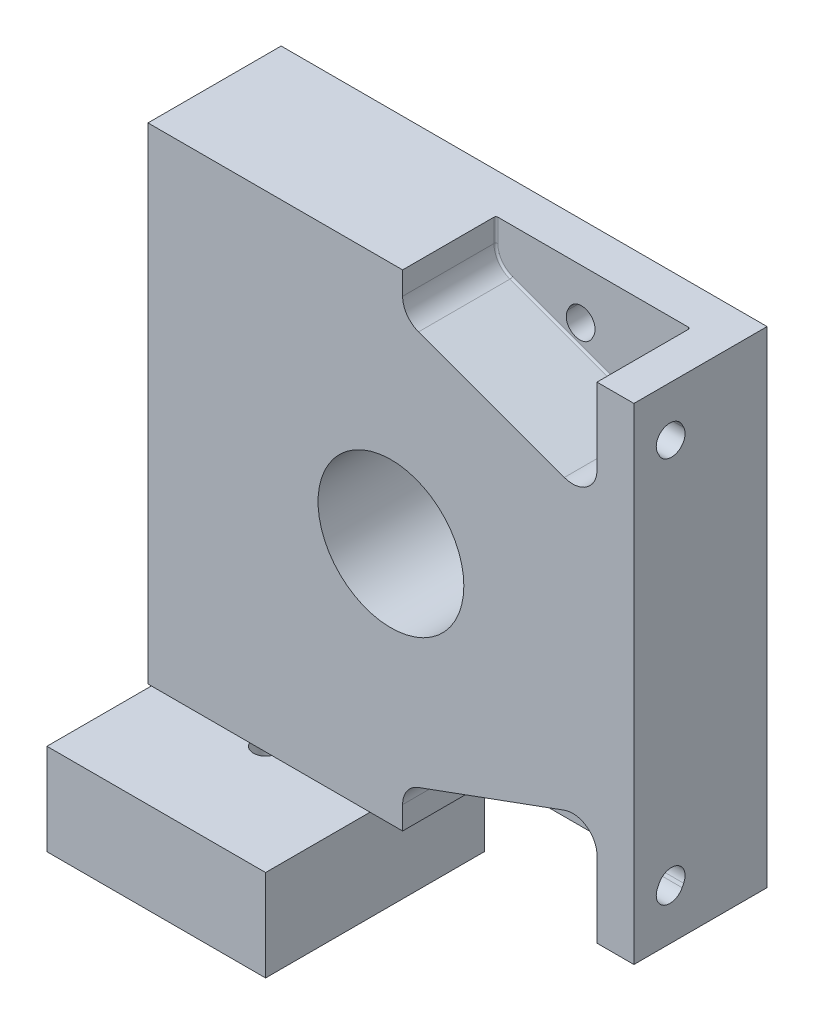
SolidWorks part; units mm, degrees
ref_plane "Front" through (0, 0, 0) normal (0, 0, 1) x (1, 0, 0)
ref_plane "Top" through (0, 0, 0) normal (0, 1, 0) x (1, 0, 0)
ref_plane "Right" through (0, 0, 0) normal (1, 0, 0) x (0, 0, -1)
sketch "Sketch2" plane through (0, 0, 0) normal (0, 0, 1) x (1, 0, 0)
  line L0 (-63.5, 63.5) -> (63.5, -63.5) construction
  line L1 (-63.5, 63.5) -> (63.5, 63.5)
  line L2 (-63.5, 63.5) -> (-63.5, -63.5)
  line L3 (-63.5, -63.5) -> (63.5, -63.5)
  line L4 (63.5, 63.5) -> (63.5, -63.5)
  dimension "D1" = 127
  dimension "D2" = 127
extrude "HOUSING" add sketch "Sketch2" along normal blind 39.5
ref_plane "Plane1" through (0, 0, 48.26) normal (0, 0, 1) x (1, 0, 0)
sketch "Sketch3" plane through (0, 0, 48.26) normal (0, 0, 1) x (1, 0, 0)
  circle A0 centre (0, 0) radius 19.05
  dimension "D1" = 38.1
sketch "Sketch4" plane through (0, 0, 39.5) normal (0, 0, 1) x (1, 0, 0)
  circle A0 centre (0, 0) radius 45.974
  dimension "D1" = 91.948
extrude "Cut-Extrude2" cut sketch "Sketch4" against normal blind 4.698 flip side to cut
sketch "Sketch8" plane through (0, 0, 34.802) normal (0, 0, 1) x (1, 0, 0)
  line L0 (3.048, -63.5) -> (3.048, -57.528)
  line L1 (-63.5, -63.5) -> (63.5, -63.5) construction
  line L2 (7.2207, -51.5629) -> (45.3207, -37.6564)
  line L3 (53.848, -43.6215) -> (53.848, -63.5)
  line L4 (-63.5, 63.5) -> (-63.5, -63.5) construction
  line L5 (3.048, -63.5) -> (53.848, -63.5)
  line L6 (0, 0) -> (83.0961, 0) construction
  line L7 (3.048, 63.5) -> (53.848, 63.5)
  line L8 (53.848, 43.6215) -> (53.848, 63.5)
  line L9 (7.2207, 51.5629) -> (45.3207, 37.6564)
  line L10 (3.048, 63.5) -> (3.048, 57.528)
  line L11 (53.848, -51.1628) -> (53.848, -17.132) construction
  line L12 (3.048, -53.086) -> (67.489, -29.5651) construction
  line L13 (3.048, -61.8074) -> (3.048, -48.2133) construction
  arc A0 (3.048, -57.528) -> (7.2207, -51.5629) centre (9.398, -57.528) cw
  arc A1 (45.3207, -37.6564) -> (53.848, -43.6215) centre (47.498, -43.6215) cw
  arc A2 (45.3207, 37.6564) -> (53.848, 43.6215) centre (47.498, 43.6215) ccw
  arc A3 (3.048, 57.528) -> (7.2207, 51.5629) centre (9.398, 57.528) ccw
  point P27 (53.848, -34.544)
  point P30 (3.048, -53.086)
  dimension "D1" = 6.35
  dimension "D2" = 50.8
  dimension "D3" = 66.548
  dimension "D4" = 28.956
  dimension "D5" = 10.414
extrude "MOUNTING POCKETS" cut sketch "Sketch8" against normal blind 24.384
sketch "Sketch21" plane through (63.5, -23.6461, 1.1666) normal (1, 0, 0) x (0, 0, -1)
  line L0 (1.1666, 111.3134) -> (1.1666, 5.23) construction
  line L1 (-54.2716, 23.6461) -> (63.3306, 23.6461) construction
  line L2 (-20.6415, 75.2421) -> (-21.0415, 76.0421)
  line L3 (-27.0254, 72.0502) -> (-27.4254, 72.8502)
  line L4 (1.1666, -39.8539) -> (1.1666, 87.1461) construction
  line L5 (-27.0254, -24.7579) -> (-27.4254, -25.5579)
  line L6 (-20.6415, -27.9498) -> (-21.0415, -28.7498)
  arc A0 (-21.0415, 76.0421) -> (-27.4254, 72.8502) centre (-24.2334, 74.4461) ccw
  arc A1 (-27.0254, 72.0502) -> (-20.6415, 75.2421) centre (-23.8334, 73.6461) ccw
  arc A2 (-27.0254, -24.7579) -> (-20.6415, -27.9498) centre (-23.8334, -26.3539) cw
  arc A3 (-21.0415, -28.7498) -> (-27.4254, -25.5579) centre (-24.2334, -27.1539) cw
  dimension "HORIZ METRIC DIST" = 25
  dimension "HORIZ ENG DIST" = 25.4
  dimension "VERTICAL METRIC DIST" = 50
  dimension "VERT ENG DIST" = 50.8
extrude "ENG_METRIC SLOT VERTICAL" cut sketch "Sketch21" against normal up to next
sketch "Sketch212" plane through (34.0621, -104.656, 0) normal (0, 0, -1) x (-1, 0, 0)
  line L0 (34.0621, 192.3232) -> (34.0621, 86.2399) construction
  line L1 (-54.2716, 104.656) -> (63.3306, 104.656) construction
  line L2 (12.254, 156.252) -> (11.854, 157.052)
  line L3 (5.8701, 153.06) -> (5.4701, 153.86)
  line L4 (5.8701, 56.252) -> (5.4701, 55.452)
  line L5 (12.254, 53.06) -> (11.854, 52.26)
  arc A0 (11.854, 157.052) -> (5.4701, 153.86) centre (8.6621, 155.456) ccw
  arc A1 (5.8701, 153.06) -> (12.254, 156.252) centre (9.0621, 154.656) ccw
  arc A2 (5.8701, 56.252) -> (12.254, 53.06) centre (9.0621, 54.656) cw
  arc A3 (11.854, 52.26) -> (5.4701, 55.452) centre (8.6621, 53.856) cw
  dimension "HORIZ METRIC DIST" = 25
  dimension "HORIZ ENG DIST" = 25.4
  dimension "VERTICAL METRIC DIST" = 50
  dimension "VERT ENG DIST" = 50.8
extrude "ENG_METRIC SLOT HORIZONTAL" cut sketch "Sketch212" against normal through all
fillet "Fillet3" radius 0.508 10 edges at (53.848, 53.5608, 10.418) (51.1378, 38.4182, 10.418) (26.2707, 44.6097, 10.418) (4.1947, 53.8882, 10.418) (3.048, 60.514, 10.418) (53.848, -53.5608, 10.418) (51.1378, -38.4182, 10.418) (26.2707, -44.6097, 10.418) (4.1947, -53.8882, 10.418) (3.048, -60.514, 10.418)
sketch "Sketch213" plane through (0, -63.5, 0) normal (0, -1, 0) x (1, 0, 0)
  line L0 (-63.5, 0) -> (63.5, 0) construction
  line L1 (-65.659, 1.905) -> (-8.509, 1.905)
  line L2 (-65.659, 1.905) -> (-65.659, 59.055)
  line L3 (-65.659, 59.055) -> (-8.509, 59.055)
  line L4 (-8.509, 1.905) -> (-8.509, 59.055)
  dimension "D1" = 57.15
  dimension "D2" = 57.15
  dimension "D3" = 1.905
  dimension "D4" = 8.509
extrude "Extrude1" add sketch "Sketch213" along normal blind 26.924
sketch "Sketch214" plane through (0, -90.424, 0) normal (0, -1, 0) x (1, 0, 0)
  line L0 (-65.659, 1.905) -> (-8.509, 1.905) construction
  line L1 (-65.659, 59.055) -> (-65.659, 1.905) construction
  circle A0 centre (-37.084, 30.48) radius 23.8125
  dimension "D3" = 47.625
  dimension "D1" = 28.575
  dimension "D2" = 28.575
extrude "Cut-Extrude3" cut sketch "Sketch214" against normal blind 5
sketch "Sketch215" plane through (0, -85.424, 0) normal (0, -1, 0) x (1, 0, 0)
  circle A0 centre (-37.084, 30.48) radius 3.175
  circle A1 centre (-37.084, 30.48) radius 23.8125 construction
  dimension "D1" = 6.35
extrude "Cut-Extrude4" cut sketch "Sketch215" against normal up to surface (21.924 mm away) up to face at (12.8058, -63.5, 15.458)
sketch "Sketch216" plane through (-65.659, 0, 0) normal (-1, 0, 0) x (0, 0, 1)
  line L1 (59.055, -63.5) -> (16.51, -63.5)
  line L2 (59.055, -63.5) -> (59.055, -66.548)
  line L3 (59.055, -66.548) -> (16.51, -66.548)
  line L4 (16.51, -63.5) -> (16.51, -66.548)
  dimension "D1" = 3.048
extrude "Cut-Extrude5" cut sketch "Sketch216" against normal up to next
hole_wizard "#8-32 Tapped Hole1" positions "Sketch218" profile "Sketch217" tap size "#8-32" standard "Ansi Inch"
sketch "Sketch218" plane through (0, -90.424, 0) normal (0, -1, 0) x (1, 0, 0)
  line L0 (-37.084, 30.48) -> (-37.084, 29.6778) construction
  line L1 (-19.7801, 30.48) -> (-37.084, 30.48) construction
  circle A0 centre (-37.084, 30.48) radius 3.175 construction
  point P0 (-60.706, 6.858)
  point P7 (-60.706, 54.102)
  point P8 (-13.462, 54.102)
  point P9 (-13.462, 6.858)
  dimension "D1" = 23.622
  dimension "D2" = 23.622
sketch "Sketch217" plane through (-60.706, -90.424, 6.858) normal (1, 0, 0) x (0, 0, -1)
  line L0 (0, 0) -> (0, 11.7464)
  line L1 (0, 11.7464) -> (1.7272, 10.7086)
  line L2 (1.7272, 10.7086) -> (1.7272, 0)
  line L5 (1.7272, 0) -> (0, 0)
  line L10 (0, 11.7464) -> (-1.7272, 10.7086) construction
  line L11 (0, -6.35) -> (0, 107.95) construction
  dimension "Tap Drill Dia." = 3.4544
  dimension "Tap Drill Depth" = 10.7086
  dimension "Drill Angle" = 118
cosmetic thread "Cosmetic Thread1" parameters "D1"=8.3312, "D2"=4.1656
sketch "Sketch239" plane through (-63.5, -121.6811, -83.5661) normal (-1, 0, 0) x (0, 0, 1)
  line L0 (102.3006, 124.3698) -> (102.3006, 122.0362)
  line L1 (101.5379, 121.2735) -> (100.4208, 121.2735)
  line L2 (99.6339, 122.0604) -> (99.6339, 124.195)
  line L3 (100.4552, 125.0162) -> (101.5379, 125.0162)
  line L4 (101.6546, 123.1805) -> (101.6546, 122.3531)
  line L5 (101.4072, 122.1057) -> (100.5491, 122.1057)
  line L6 (100.3049, 122.3499) -> (100.3049, 123.8847)
  line L7 (100.5701, 124.1499) -> (101.4117, 124.1499)
  line L8 (101.659, 123.901) -> (101.6546, 123.1805)
  line L9 (101.6214, 127.7512) -> (101.6214, 126.2045)
  line L10 (101.4803, 126.0635) -> (101.1416, 126.0635)
  line L11 (100.9953, 126.2098) -> (100.9953, 127.7512)
  line L12 (100.9953, 127.7512) -> (101.6214, 127.7512)
  line L13 (102.3006, 128.5943) -> (102.3006, 125.7347)
  line L14 (101.7926, 125.2267) -> (101.2545, 125.2267)
  line L15 (99.6339, 125.2267) -> (99.6339, 126.0693)
  line L16 (99.6339, 126.0693) -> (100.1002, 126.0693)
  line L17 (100.3288, 126.2979) -> (100.3288, 127.7582)
  line L18 (100.3288, 127.7582) -> (99.6339, 127.7582)
  line L19 (99.6339, 127.7582) -> (99.6339, 128.5943)
  line L20 (99.6339, 128.5943) -> (102.3006, 128.5943)
  line L21 (101.3052, 111.8683) -> (101.3052, 111.033)
  line L22 (101.3052, 111.033) -> (101.7294, 111.033)
  line L23 (102.3006, 111.6043) -> (102.3006, 113.7376)
  line L24 (101.5923, 114.4459) -> (100.3232, 114.4459)
  line L25 (99.6339, 113.7566) -> (99.6339, 111.4732)
  line L26 (100.1192, 110.9879) -> (100.6227, 110.9879)
  line L27 (100.6227, 110.9879) -> (100.6227, 111.8368)
  line L28 (100.6227, 111.8368) -> (100.4696, 111.8368)
  line L29 (100.2358, 112.0705) -> (100.2358, 113.3006)
  line L30 (100.5426, 113.6074) -> (101.3217, 113.6074)
  line L31 (101.6185, 113.3107) -> (101.6185, 112.0939)
  line L32 (101.3929, 111.8683) -> (101.3052, 111.8683)
  line L33 (99.6339, 136.1587) -> (102.3006, 134.699)
  line L34 (102.3006, 134.699) -> (102.3006, 133.4017)
  line L35 (102.3006, 133.4017) -> (99.6339, 131.9711)
  line L36 (99.6339, 131.9711) -> (99.6339, 132.9287)
  line L37 (99.6339, 132.9287) -> (100.0922, 133.1628)
  line L38 (100.0922, 133.1628) -> (100.0922, 134.9283)
  line L39 (100.0922, 134.9283) -> (99.6339, 135.1676)
  line L40 (99.6339, 135.1676) -> (99.6339, 136.1587)
  line L41 (100.7046, 134.6309) -> (100.7046, 133.468)
  line L42 (100.7046, 133.468) -> (101.6586, 133.9731)
  line L43 (101.6586, 133.9731) -> (101.6586, 134.1258)
  line L44 (101.6586, 134.1258) -> (100.7046, 134.6309)
  line L45 (102.3006, 131.8571) -> (102.3006, 128.8708)
  line L46 (102.3006, 128.8708) -> (101.6626, 128.8708)
  line L47 (101.6626, 128.8708) -> (101.6626, 131.0623)
  line L48 (101.6626, 131.0623) -> (101.2925, 131.0623)
  line L49 (101.2925, 131.0623) -> (101.2925, 128.9844)
  line L50 (101.2925, 128.9844) -> (100.693, 128.9844)
  line L51 (100.693, 128.9844) -> (100.693, 131.0623)
  line L52 (100.693, 131.0623) -> (100.2774, 131.0623)
  line L53 (100.2774, 131.0623) -> (100.2774, 128.8708)
  line L54 (100.2774, 128.8708) -> (99.6339, 128.8708)
  line L55 (99.6339, 128.8708) -> (99.6339, 131.8571)
  line L56 (99.6339, 131.8571) -> (102.3006, 131.8571)
  line L57 (102.3006, 121.1265) -> (102.3006, 117.8159)
  line L58 (102.3006, 117.8159) -> (101.6106, 117.8159)
  line L59 (101.6106, 117.8159) -> (101.6106, 119.0485)
  line L60 (101.6106, 119.0485) -> (99.6339, 119.0485)
  line L61 (99.6339, 119.0485) -> (99.6339, 119.9334)
  line L62 (99.6339, 119.9334) -> (101.6102, 119.9334)
  line L63 (101.6102, 119.9334) -> (101.6102, 121.1265)
  line L64 (101.6102, 121.1265) -> (102.3006, 121.1265)
  line L65 (102.3006, 117.6536) -> (102.3006, 114.6497)
  line L66 (102.3006, 114.6497) -> (101.6621, 114.6497)
  line L67 (101.6621, 114.6497) -> (101.6621, 116.8274)
  line L68 (101.6621, 116.8274) -> (101.2997, 116.8274)
  line L69 (101.2997, 116.8274) -> (101.2997, 114.7563)
  line L70 (101.2997, 114.7563) -> (100.6993, 114.7563)
  line L71 (100.6993, 114.7563) -> (100.6993, 116.8274)
  line L72 (100.6993, 116.8274) -> (100.2804, 116.8274)
  line L73 (100.2804, 116.8274) -> (100.2804, 114.6497)
  line L74 (100.2804, 114.6497) -> (99.6339, 114.6497)
  line L75 (99.6339, 114.6497) -> (99.6339, 117.6536)
  line L76 (99.6339, 117.6536) -> (102.3006, 117.6536)
  line L77 (102.3006, 110.7071) -> (102.3006, 109.8385)
  line L78 (102.3006, 109.8385) -> (101.3454, 109.8385)
  line L79 (101.3454, 109.8385) -> (101.3454, 108.0035)
  line L80 (101.3454, 108.0035) -> (102.3006, 108.0035)
  line L81 (102.3006, 108.0035) -> (102.3006, 107.1132)
  line L82 (102.3006, 107.1132) -> (99.6339, 107.1132)
  line L83 (99.6339, 107.1132) -> (99.6339, 108.0035)
  line L84 (99.6339, 108.0035) -> (100.5967, 108.0035)
  line L85 (100.5967, 108.0035) -> (100.5967, 109.8385)
  line L86 (100.5967, 109.8385) -> (99.6339, 109.8385)
  line L87 (99.6339, 109.8385) -> (99.6339, 110.7071)
  line L88 (99.6339, 110.7071) -> (102.3006, 110.7071)
  line L89 (98.9126, 131.6685) -> (98.9126, 128.6152)
  line L90 (98.9126, 128.6152) -> (91.9852, 121.7251)
  line L91 (91.9852, 121.7251) -> (96.8043, 116.8798)
  line L92 (96.8043, 116.8798) -> (96.8043, 124.7941)
  line L93 (96.8043, 124.7941) -> (98.9126, 126.8817)
  line L94 (98.9126, 126.8817) -> (98.9126, 111.5851)
  line L95 (98.9126, 111.5851) -> (88.8711, 121.6811)
  line L96 (88.8711, 121.6811) -> (98.9126, 131.6685)
  line L97 (103.0216, 131.6685) -> (113.0631, 121.6811)
  line L98 (113.0631, 121.6811) -> (103.0216, 111.5851)
  line L99 (103.0216, 131.6685) -> (103.0216, 128.6152)
  line L100 (103.0216, 128.6152) -> (109.985, 121.6893)
  line L101 (109.985, 121.6893) -> (105.1659, 116.844)
  line L102 (105.1659, 116.844) -> (105.1659, 124.7583)
  line L103 (105.1659, 124.7583) -> (103.0216, 126.8089)
  line L104 (103.0216, 126.8089) -> (103.0216, 111.5851)
  line L105 (100.3283, 125.2267) -> (99.6339, 125.2267)
  line L106 (118.3681, 121.6811) -> (83.5661, 121.6811) construction
  line L107 (118.3681, 75.7071) -> (118.3681, 167.6551) construction
  line L108 (113.0631, 121.6811) -> (88.8711, 121.6811) construction
  arc A0 (102.3006, 122.0362) -> (101.5379, 121.2735) centre (101.5379, 122.0362) cw
  arc A1 (100.4208, 121.2735) -> (99.6339, 122.0604) centre (100.4208, 122.0604) cw
  arc A2 (99.6339, 124.195) -> (100.4552, 125.0162) centre (100.4552, 124.195) cw
  arc A3 (101.5379, 125.0162) -> (102.3006, 124.3698) centre (101.5379, 124.2431) cw
  arc A4 (101.6546, 122.3531) -> (101.4072, 122.1057) centre (101.4072, 122.3531) cw
  arc A5 (100.5491, 122.1057) -> (100.3049, 122.3499) centre (100.5491, 122.3499) cw
  arc A6 (100.3049, 123.8847) -> (100.5701, 124.1499) centre (100.5701, 123.8847) cw
  arc A7 (101.4117, 124.1499) -> (101.659, 123.901) centre (101.4117, 123.9025) cw
  arc A8 (101.6214, 126.2045) -> (101.4803, 126.0635) centre (101.4803, 126.2045) cw
  arc A9 (101.1416, 126.0635) -> (100.9953, 126.2098) centre (101.1416, 126.2098) cw
  arc A10 (100.1002, 126.0693) -> (100.3288, 126.2979) centre (100.1002, 126.2979) ccw
  arc A11 (101.7926, 125.2267) -> (102.3006, 125.7347) centre (101.7926, 125.7347) ccw
  arc A12 (101.2545, 125.2267) -> (100.7973, 125.6839) centre (101.2545, 125.6839) cw
  arc A13 (100.7973, 125.6839) -> (100.3283, 125.2267) centre (100.34, 125.6839) cw
  arc A14 (101.7294, 111.033) -> (102.3006, 111.6043) centre (101.7294, 111.6043) ccw
  arc A15 (102.3006, 113.7376) -> (101.5923, 114.4459) centre (101.5923, 113.7376) ccw
  arc A16 (100.3232, 114.4459) -> (99.6339, 113.7566) centre (100.3232, 113.7566) ccw
  arc A17 (99.6339, 111.4732) -> (100.1192, 110.9879) centre (100.1192, 111.4732) ccw
  arc A18 (100.4696, 111.8368) -> (100.2358, 112.0705) centre (100.4696, 112.0705) cw
  arc A19 (100.2358, 113.3006) -> (100.5426, 113.6074) centre (100.5426, 113.3006) cw
  arc A20 (101.3217, 113.6074) -> (101.6185, 113.3107) centre (101.3217, 113.3107) cw
  arc A21 (101.6185, 112.0939) -> (101.3929, 111.8683) centre (101.3929, 112.0939) cw
extrude "AEROTECH5" [suppressed] cut sketch "Sketch239" against normal blind 0.1
sketch "Sketch240" plane through (80.6623, 63.5, -107.4581) normal (0, 1, 0) x (-1, 0, 0)
  line L0 (108.1996, 126.0312) -> (110.5333, 126.0312)
  line L1 (111.2959, 125.2686) -> (111.2959, 124.1515)
  line L2 (110.509, 123.3646) -> (108.3744, 123.3646)
  line L3 (107.5532, 124.1858) -> (107.5532, 125.2685)
  line L4 (109.3889, 125.3852) -> (110.2163, 125.3852)
  line L5 (110.4637, 125.1378) -> (110.4637, 124.2797)
  line L6 (110.2195, 124.0355) -> (108.6847, 124.0355)
  line L7 (108.4195, 124.3007) -> (108.4195, 125.1423)
  line L8 (108.6684, 125.3896) -> (109.3889, 125.3852)
  line L9 (104.8182, 125.352) -> (106.3649, 125.352)
  line L10 (106.5059, 125.211) -> (106.5059, 124.8722)
  line L11 (106.3597, 124.726) -> (104.8182, 124.726)
  line L12 (104.8182, 124.726) -> (104.8182, 125.352)
  line L13 (103.9751, 126.0312) -> (106.8348, 126.0312)
  line L14 (107.3428, 125.5232) -> (107.3428, 124.9851)
  line L15 (107.3428, 123.3646) -> (106.5001, 123.3646)
  line L16 (106.5001, 123.3646) -> (106.5001, 123.8308)
  line L17 (106.2715, 124.0594) -> (104.8112, 124.0594)
  line L18 (104.8112, 124.0594) -> (104.8112, 123.3646)
  line L19 (104.8112, 123.3646) -> (103.9751, 123.3646)
  line L20 (103.9751, 123.3646) -> (103.9751, 126.0312)
  line L21 (120.7011, 125.0358) -> (121.5364, 125.0358)
  line L22 (121.5364, 125.0358) -> (121.5364, 125.46)
  line L23 (120.9652, 126.0312) -> (118.8318, 126.0312)
  line L24 (118.1235, 125.3229) -> (118.1235, 124.0538)
  line L25 (118.8128, 123.3646) -> (121.0962, 123.3646)
  line L26 (121.5815, 123.8498) -> (121.5815, 124.3533)
  line L27 (121.5815, 124.3533) -> (120.7327, 124.3533)
  line L28 (120.7327, 124.3533) -> (120.7327, 124.2002)
  line L29 (120.4989, 123.9664) -> (119.2688, 123.9664)
  line L30 (118.962, 124.2732) -> (118.962, 125.0523)
  line L31 (119.2587, 125.3491) -> (120.4755, 125.3491)
  line L32 (120.7011, 125.1235) -> (120.7011, 125.0358)
  line L33 (96.4107, 123.3646) -> (97.8704, 126.0312)
  line L34 (97.8704, 126.0312) -> (99.1677, 126.0312)
  line L35 (99.1677, 126.0312) -> (100.5983, 123.3646)
  line L36 (100.5983, 123.3646) -> (99.6408, 123.3646)
  line L37 (99.6408, 123.3646) -> (99.4066, 123.8228)
  line L38 (99.4066, 123.8228) -> (97.6412, 123.8228)
  line L39 (97.6412, 123.8228) -> (97.4018, 123.3646)
  line L40 (97.4018, 123.3646) -> (96.4107, 123.3646)
  line L41 (97.9385, 124.4352) -> (99.1014, 124.4352)
  line L42 (99.1014, 124.4352) -> (98.5963, 125.3892)
  line L43 (98.5963, 125.3892) -> (98.4436, 125.3892)
  line L44 (98.4436, 125.3892) -> (97.9385, 124.4352)
  line L45 (100.7123, 126.0312) -> (103.6986, 126.0312)
  line L46 (103.6986, 126.0312) -> (103.6986, 125.3933)
  line L47 (103.6986, 125.3933) -> (101.5071, 125.3933)
  line L48 (101.5071, 125.3933) -> (101.5071, 125.0231)
  line L49 (101.5071, 125.0231) -> (103.585, 125.0231)
  line L50 (103.585, 125.0231) -> (103.585, 124.4236)
  line L51 (103.585, 124.4236) -> (101.5071, 124.4236)
  line L52 (101.5071, 124.4236) -> (101.5071, 124.008)
  line L53 (101.5071, 124.008) -> (103.6986, 124.008)
  line L54 (103.6986, 124.008) -> (103.6986, 123.3646)
  line L55 (103.6986, 123.3646) -> (100.7123, 123.3646)
  line L56 (100.7123, 123.3646) -> (100.7123, 126.0312)
  line L57 (111.4429, 126.0312) -> (114.7535, 126.0312)
  line L58 (114.7535, 126.0312) -> (114.7535, 125.3412)
  line L59 (114.7535, 125.3412) -> (113.5209, 125.3412)
  line L60 (113.5209, 125.3412) -> (113.5209, 123.3646)
  line L61 (113.5209, 123.3646) -> (112.636, 123.3646)
  line L62 (112.636, 123.3646) -> (112.636, 125.3408)
  line L63 (112.636, 125.3408) -> (111.4429, 125.3408)
  line L64 (111.4429, 125.3408) -> (111.4429, 126.0312)
  line L65 (114.9158, 126.0312) -> (117.9197, 126.0312)
  line L66 (117.9197, 126.0312) -> (117.9197, 125.3927)
  line L67 (117.9197, 125.3927) -> (115.742, 125.3927)
  line L68 (115.742, 125.3927) -> (115.742, 125.0303)
  line L69 (115.742, 125.0303) -> (117.8131, 125.0303)
  line L70 (117.8131, 125.0303) -> (117.8131, 124.43)
  line L71 (117.8131, 124.43) -> (115.742, 124.43)
  line L72 (115.742, 124.43) -> (115.742, 124.0111)
  line L73 (115.742, 124.0111) -> (117.9197, 124.0111)
  line L74 (117.9197, 124.0111) -> (117.9197, 123.3646)
  line L75 (117.9197, 123.3646) -> (114.9158, 123.3646)
  line L76 (114.9158, 123.3646) -> (114.9158, 126.0312)
  line L77 (121.8623, 126.0312) -> (122.7309, 126.0312)
  line L78 (122.7309, 126.0312) -> (122.7309, 125.076)
  line L79 (122.7309, 125.076) -> (124.5659, 125.076)
  line L80 (124.5659, 125.076) -> (124.5659, 126.0312)
  line L81 (124.5659, 126.0312) -> (125.4563, 126.0312)
  line L82 (125.4563, 126.0312) -> (125.4563, 123.3646)
  line L83 (125.4563, 123.3646) -> (124.5659, 123.3646)
  line L84 (124.5659, 123.3646) -> (124.5659, 124.3273)
  line L85 (124.5659, 124.3273) -> (122.7309, 124.3273)
  line L86 (122.7309, 124.3273) -> (122.7309, 123.3646)
  line L87 (122.7309, 123.3646) -> (121.8623, 123.3646)
  line L88 (121.8623, 123.3646) -> (121.8623, 126.0312)
  line L89 (100.9009, 122.6432) -> (103.9543, 122.6432)
  line L90 (103.9543, 122.6432) -> (110.8443, 115.7158)
  line L91 (110.8443, 115.7158) -> (115.6896, 120.535)
  line L92 (115.6896, 120.535) -> (107.7753, 120.535)
  line L93 (107.7753, 120.535) -> (105.6877, 122.6432)
  line L94 (105.6877, 122.6432) -> (120.9843, 122.6432)
  line L95 (120.9843, 122.6432) -> (110.8883, 112.6017)
  line L96 (110.8883, 112.6017) -> (100.9009, 122.6432)
  line L97 (100.9009, 126.7523) -> (110.8883, 136.7938)
  line L98 (110.8883, 136.7938) -> (120.9843, 126.7523)
  line L99 (100.9009, 126.7523) -> (103.9543, 126.7523)
  line L100 (103.9543, 126.7523) -> (110.8801, 133.7157)
  line L101 (110.8801, 133.7157) -> (115.7254, 128.8965)
  line L102 (115.7254, 128.8965) -> (107.8111, 128.8965)
  line L103 (107.8111, 128.8965) -> (105.7606, 126.7523)
  line L104 (105.7606, 126.7523) -> (120.9843, 126.7523)
  line L105 (107.3428, 124.059) -> (107.3428, 123.3646)
  line L106 (110.8883, 136.7938) -> (110.8883, 112.6017) construction
  line L107 (110.8883, 142.2601) -> (110.8883, 107.4581) construction
  line L108 (77.6143, 142.2601) -> (144.1623, 142.2601) construction
  line L109 (17.1623, 107.4581) -> (144.1623, 107.4581) construction
  arc A0 (110.5333, 126.0312) -> (111.2959, 125.2686) centre (110.5333, 125.2686) cw
  arc A1 (111.2959, 124.1515) -> (110.509, 123.3646) centre (110.509, 124.1515) cw
  arc A2 (108.3744, 123.3646) -> (107.5532, 124.1858) centre (108.3744, 124.1858) cw
  arc A3 (107.5532, 125.2685) -> (108.1996, 126.0312) centre (108.3264, 125.2685) cw
  arc A4 (110.2163, 125.3852) -> (110.4637, 125.1378) centre (110.2163, 125.1378) cw
  arc A5 (110.4637, 124.2797) -> (110.2195, 124.0355) centre (110.2195, 124.2797) cw
  arc A6 (108.6847, 124.0355) -> (108.4195, 124.3007) centre (108.6847, 124.3007) cw
  arc A7 (108.4195, 125.1423) -> (108.6684, 125.3896) centre (108.6669, 125.1423) cw
  arc A8 (106.3649, 125.352) -> (106.5059, 125.211) centre (106.3649, 125.211) cw
  arc A9 (106.5059, 124.8722) -> (106.3597, 124.726) centre (106.3597, 124.8722) cw
  arc A10 (106.5001, 123.8308) -> (106.2715, 124.0594) centre (106.2715, 123.8308) ccw
  arc A11 (107.3428, 125.5232) -> (106.8348, 126.0312) centre (106.8348, 125.5232) ccw
  arc A12 (107.3428, 124.9851) -> (106.8856, 124.5279) centre (106.8856, 124.9851) cw
  arc A13 (106.8856, 124.5279) -> (107.3428, 124.059) centre (106.8856, 124.0706) cw
  arc A14 (121.5364, 125.46) -> (120.9652, 126.0312) centre (120.9652, 125.46) ccw
  arc A15 (118.8318, 126.0312) -> (118.1235, 125.3229) centre (118.8318, 125.3229) ccw
  arc A16 (118.1235, 124.0538) -> (118.8128, 123.3646) centre (118.8128, 124.0538) ccw
  arc A17 (121.0962, 123.3646) -> (121.5815, 123.8498) centre (121.0962, 123.8498) ccw
  arc A18 (120.7327, 124.2002) -> (120.4989, 123.9664) centre (120.4989, 124.2002) cw
  arc A19 (119.2688, 123.9664) -> (118.962, 124.2732) centre (119.2688, 124.2732) cw
  arc A20 (118.962, 125.0523) -> (119.2587, 125.3491) centre (119.2587, 125.0523) cw
  arc A21 (120.4755, 125.3491) -> (120.7011, 125.1235) centre (120.4755, 125.1235) cw
extrude "Cut-Extrude6" [suppressed] cut sketch "Sketch240" against normal blind 0.1
sketch "Sketch241" plane through (0, 0, 39.5) normal (0, 0, 1) x (1, 0, 0)
  circle A0 centre (0, 0) radius 45.974
  circle A1 centre (0, 0) radius 45.974 construction
extrude "Cut-Extrude7" cut sketch "Sketch241" against normal up to surface (4.698 mm away) up to face at (20.8684, 0, 34.802)
extrude "Cut-Extrude8" cut sketch "Sketch3" against normal through all
ref_axis "Axis1" through (0, 0, -2.9527) along (0, 0, 1)
ref_plane "Plane2" through (0, 0, 0) normal (0, 1, 0) x (0, 0, 1)
